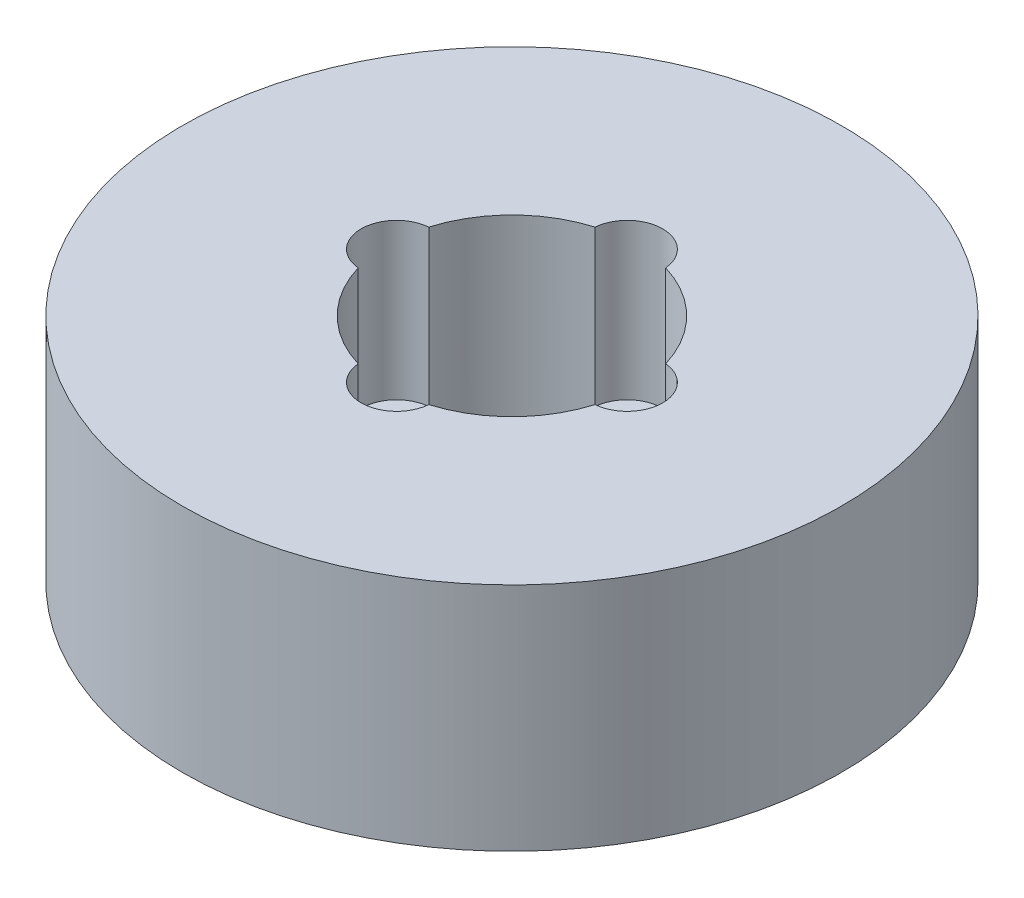
SolidWorks part; units mm, degrees
ref_plane "Front Plane" through (0, 0, 0) normal (0, 0, 1) x (1, 0, 0)
ref_plane "Top Plane" through (0, 0, 0) normal (0, 1, 0) x (1, 0, 0)
ref_plane "Right Plane" through (0, 0, 0) normal (1, 0, 0) x (0, 0, -1)
sketch "Sketch1" plane through (0, 0, 0) normal (0, 1, 0) x (1, 0, 0)
  circle A0 centre (0, 0) radius 20
  dimension "FLANGE_OD" = 40
extrude "Boss-Extrude1" add sketch "Sketch1" along normal blind 14
sketch "Sketch2" plane through (0, 0, 0) normal (0, 1, 0) x (1, 0, 0)
  circle A0 centre (0, 0) radius 7.5
  dimension "BORE_D" = 15
extrude "Cut-Extrude1" cut sketch "Sketch2" along normal through all
sketch "Sketch3" plane through (0, 14, 0) normal (0, 1, 0) x (1, 0, 0)
  circle A0 centre (0, 0) radius 6.9981 construction
  circle A1 centre (-6.9981, 0) radius 2.1518
  dimension "BOLT_D" = 4.3036
  dimension "BOLT_PCD" = 13.9962
extrude "Cut-Extrude2" cut sketch "Sketch3" against normal blind 9.4315
pattern_circular "CirPattern1" count 4 over 360 about axis through (0, 0, 0) along (0, 1, 0) of "Cut-Extrude2"
